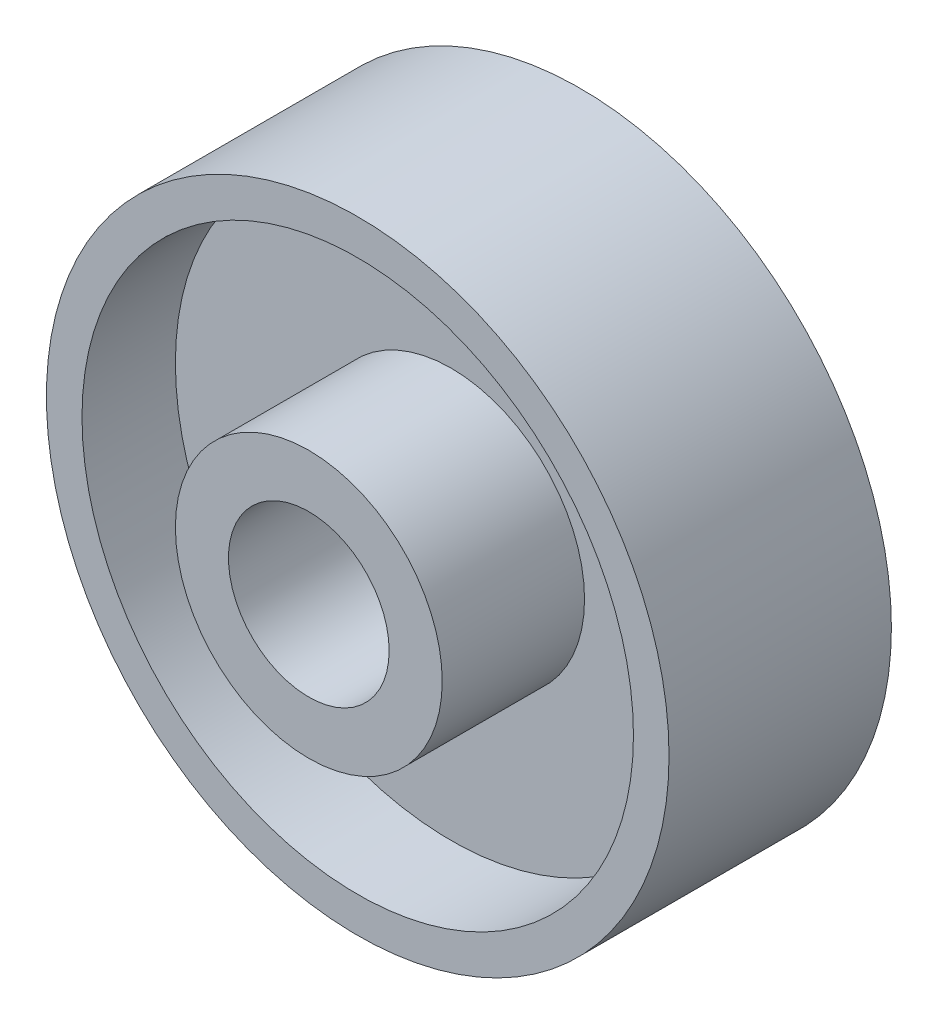
SolidWorks part; units mm, degrees
material "Commercial Bronze, UNS C22000 (90-10 Bronze)"
ref_plane "Front Plane" through (0, 0, 0) normal (0, 0, 1) x (1, 0, 0)
ref_plane "Top Plane" through (0, 0, 0) normal (0, 1, 0) x (1, 0, 0)
ref_plane "Right Plane" through (0, 0, 0) normal (1, 0, 0) x (0, 0, -1)
sketch "Sketch1" plane through (0, 0, 0) normal (0, 0, 1) x (1, 0, 0)
  circle A0 centre (0, 0) radius 18.065
  circle A1 centre (0, 0) radius 30
  circle A2 centre (0, 0) radius 70
  circle A3 centre (0, 0) radius 62
  dimension "D1" = 60
  dimension "D2" = 36.13
  dimension "D3" = 124
  dimension "D4" = 140
  dimension "D5" = 32
  dimension "D7" = 36.13
extrude "Boss-Extrude1" add sketch "Sketch1" along normal blind 36 and the other way blind 36 contours A1 A0 region at (-29.1515, 0, 0)
extrude "Boss-Extrude2" add sketch "Sketch1<3>" along normal blind 4 and the other way blind 4 contours A3 A1 region at (-60.2464, 0, 0)
sketch "Sketch1<3>" plane through (0, 0, 0) normal (0, 0, 1) x (1, 0, 0) same geometry as "Sketch1"
extrude "Boss-Extrude3" add sketch "Sketch1<4>" along normal blind 25 and the other way blind 25 contours A2 A3 region at (-68.0201, 0, 0)
sketch "Sketch1<4>" plane through (0, 0, 0) normal (0, 0, 1) x (1, 0, 0) same geometry as "Sketch1"
